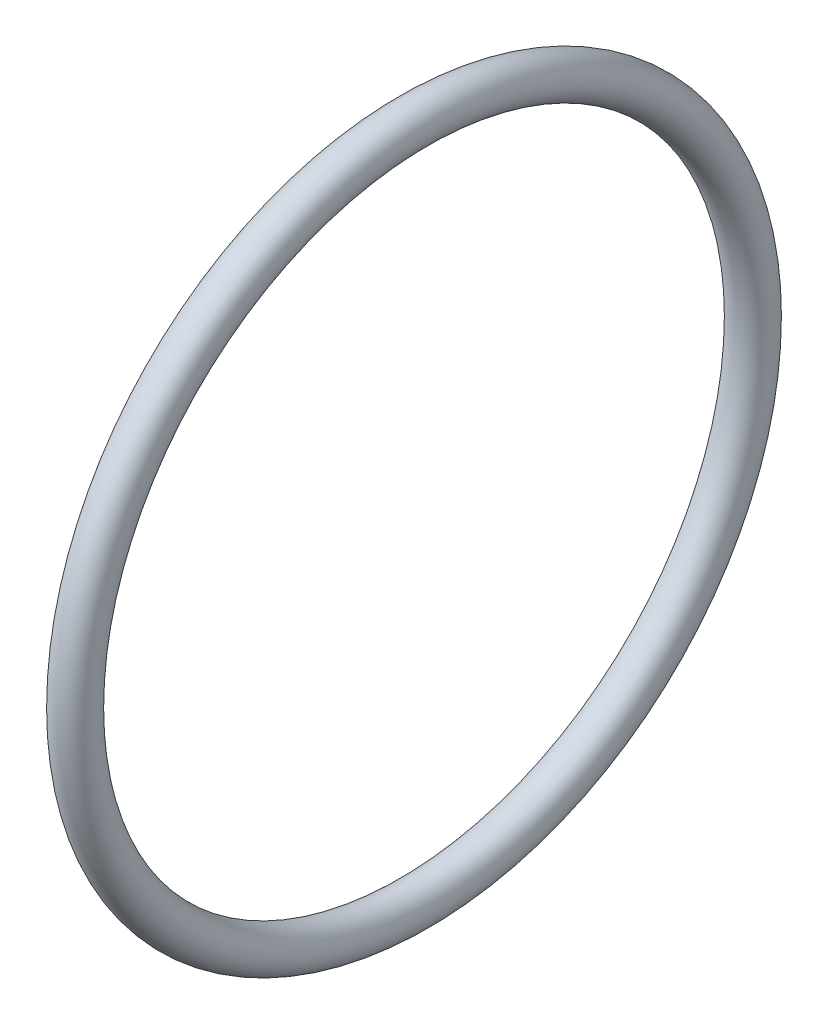
SolidWorks part; units mm, degrees
ref_plane "Front Plane" through (0, 0, 0) normal (0, 0, 1) x (1, 0, 0)
ref_plane "Top Plane" through (0, 0, 0) normal (0, 1, 0) x (1, 0, 0)
ref_plane "Right Plane" through (0, 0, 0) normal (1, 0, 0) x (0, 0, -1)
sketch "Sketch2" plane through (0, 0, 0) normal (0, 0, 1) x (1, 0, 0)
  line L0 (0, 0) -> (58.591, 0) construction
  line L2 (0, 0) -> (18.4, 0)
  line L3 (0, 0) -> (0, 2.5)
  line L4 (0, 2.5) -> (18.4, 2.5)
  line L5 (18.4, 0) -> (18.4, 2.5)
  line L6 (6.0094, 2.5) -> (6.0094, 6)
  line L11 (6.0094, 6) -> (9.9794, 6)
  line L16 (12.9794, 6) -> (12.9794, 3)
  line L17 (12.9794, 3) -> (13.6398, 3)
  line L18 (13.6398, 3) -> (13.6398, 2.5)
  line L19 (13.6398, 2.5) -> (6.0094, 2.5)
  line L22 (13.6398, 2.5) -> (16.1198, 2.5)
  line L23 (13.6398, 2.5) -> (13.6398, 4)
  line L24 (13.6398, 4) -> (16.1198, 4)
  line L25 (16.1198, 2.5) -> (16.1198, 4)
  line L27 (6.0094, 6) -> (9.9794, 6)
  line L28 (6.0094, 6) -> (6.0094, 9)
  line L29 (6.0094, 9) -> (9.9794, 9)
  line L30 (9.9794, 6) -> (9.9794, 9)
  line L31 (6.0094, 9) -> (6.0094, 8.25)
  line L32 (6.0094, 8.25) -> (5.0094, 8.25)
  line L33 (8.6609, 22.001) -> (8.6609, 12.476) construction
  line L34 (5.0094, 12.476) -> (12.3124, 12.476)
  line L35 (9.9794, 9) -> (12.3124, 9)
  line L36 (5.0094, 7.9375) -> (1.8344, 7.9375)
  line L37 (5.0094, 8.25) -> (5.0094, 12.476)
  line L38 (5.0094, 7.9375) -> (5.0094, 13.9365)
  line L39 (5.0094, 13.9365) -> (1.8344, 13.9365)
  line L40 (1.8344, 7.9375) -> (1.8344, 13.9365)
  line L41 (5.0094, 22.001) -> (12.3124, 22.001)
  line L42 (5.0094, 22.001) -> (5.0094, 30.1625)
  line L43 (5.0094, 30.1625) -> (12.3124, 30.1625)
  line L44 (12.3124, 22.001) -> (12.3124, 30.1625)
  line L49 (16.6398, 22.001) -> (16.6398, 7.5)
  line L51 (23.0198, 7.5) -> (23.0198, 6.5)
  line L54 (16.1198, 4) -> (13.6398, 4)
  line L56 (18.0398, 7.5) -> (23.0198, 7.5)
  line L57 (13.3124, 22.001) -> (16.6398, 22.001)
  line L58 (16.1198, 3.5) -> (20.0198, 3.5)
  line L59 (29.9098, 14) -> (26.9098, 11)
  line L60 (4.0094, 31.75) -> (18.0398, 31.75)
  line L61 (18.0398, 7.5) -> (23.0198, 7.5)
  line L62 (18.0398, 7.5) -> (18.0398, 12)
  line L63 (18.0398, 12) -> (23.0198, 12)
  line L64 (23.0198, 7.5) -> (23.0198, 12)
  line L65 (18.0398, 31.75) -> (18.0398, 12)
  line L66 (23.0198, 11) -> (26.9098, 11)
  line L67 (34.8098, 23) -> (31.3098, 19.5)
  line L68 (35.8098, 31) -> (38.7998, 33.99)
  line L69 (29.9098, 14) -> (29.9098, 15)
  line L70 (29.9098, 15) -> (22.9398, 15)
  line L71 (22.9398, 15) -> (21.0398, 15)
  line L72 (18.0398, 7.5) -> (16.6398, 7.5)
  line L73 (21.0398, 15) -> (21.0398, 43)
  line L74 (19.5798, 40) -> (9.6198, 40)
  line L75 (9.6198, 40) -> (4.0094, 40)
  line L76 (21.0398, 43) -> (19.5798, 43)
  line L77 (22.9398, 15) -> (29.9098, 15)
  line L78 (22.9398, 15) -> (22.9398, 21)
  line L79 (22.9398, 21) -> (29.9098, 21)
  line L80 (29.9098, 15) -> (29.9098, 21)
  line L81 (9.6198, 40) -> (19.5798, 40)
  line L82 (9.6198, 40) -> (9.6198, 50)
  line L83 (9.6198, 50) -> (19.5798, 50)
  line L84 (19.5798, 40) -> (19.5798, 50)
  line L85 (4.0094, 40) -> (4.0094, 31.75)
  line L86 (12.9794, 3) -> (12.9794, 2.5)
  line L87 (31.3098, 19.5) -> (29.9098, 19.5)
  line L88 (21.4694, 63.5) -> (21.4694, 51.308)
  line L89 (21.4694, 63.5) -> (25.9398, 63.5)
  line L90 (25.9398, 63.5) -> (25.9398, 25)
  line L91 (27.8398, 25) -> (25.9398, 25)
  line L92 (9.6198, 48) -> (8.1598, 48)
  line L93 (8.1598, 48) -> (8.1598, 53.476)
  line L94 (8.1598, 53.476) -> (19.5798, 53.476)
  line L95 (19.5798, 53.476) -> (19.5798, 50)
  line L96 (13.8698, 63.001) -> (13.8698, 53.476) construction
  line L97 (8.1598, 63.001) -> (19.5798, 63.001)
  line L98 (8.1598, 63.001) -> (8.1598, 68.2625)
  line L99 (8.1598, 68.2625) -> (19.5798, 68.2625)
  line L100 (19.5798, 63.001) -> (19.5798, 68.2625)
  line L101 (12.9794, 6) -> (11.9794, 6)
  line L102 (8.1598, 44.825) -> (4.9848, 44.825)
  line L103 (8.1598, 44.825) -> (8.1598, 54.9365)
  line L104 (8.1598, 54.9365) -> (4.9848, 54.9365)
  line L106 (9.9794, 6) -> (10.8794, 6)
  line L107 (27.8398, 25) -> (34.8098, 25)
  line L108 (34.8098, 25) -> (34.8098, 23)
  line L109 (0, 0) -> (-2, 0)
  line L110 (0, 0) -> (0, 11)
  line L111 (27.8398, 25) -> (34.8098, 25)
  line L112 (27.8398, 25) -> (27.8398, 32.5)
  line L113 (27.8398, 32.5) -> (34.8098, 32.5)
  line L114 (34.8098, 25) -> (34.8098, 32.5)
  line L115 (35.8098, 31) -> (34.8098, 31)
  line L116 (27.8398, 32.5) -> (27.8398, 64.5)
  line L117 (20.5373, 74.025) -> (6.2023, 74.025)
  line L118 (6.2023, 74.025) -> (6.2023, 76.2)
  line L119 (38.7998, 47.29) -> (30.8398, 55.25)
  line L120 (0, 11) -> (-2, 11)
  line L121 (38.7998, 43.815) -> (30.8623, 43.815)
  line L123 (-4.8152, 69.85) -> (1.5348, 76.2)
  line L124 (38.7998, 47.29) -> (38.7998, 33.99)
  line L125 (-2, 0) -> (-2, 11)
  line L126 (38.7998, 37.465) -> (30.8623, 37.465)
  line L127 (30.8623, 43.815) -> (30.8623, 37.465)
  line L128 (6.0094, 2.5) -> (6.0094, 0)
  line L129 (-0.0152, 63.5) -> (-0.0152, 30)
  line L132 (4.9848, 63.5) -> (-0.0152, 63.5)
  line L136 (-1.8152, 30) -> (-11.7752, 30)
  line L138 (-13.7752, 25.4) -> (-2, 25.4)
  line L139 (-2, 25.4) -> (-2, 11.5)
  line L140 (27.8398, 64.5) -> (20.5373, 64.5)
  line L141 (-1.8152, 30) -> (-11.7752, 30)
  line L142 (-1.8152, 30) -> (-1.8152, 39)
  line L143 (-1.8152, 39) -> (-11.7752, 39)
  line L144 (-11.7752, 30) -> (-11.7752, 39)
  line L145 (20.5373, 64.5) -> (20.5373, 74.025)
  line L146 (-12.7752, 37) -> (-12.7752, 47.29)
  line L147 (-12.7752, 37) -> (-11.7752, 37)
  line L148 (30.8398, 55.25) -> (30.8398, 76.2)
  line L149 (11.9794, 6) -> (11.9794, 5.45)
  line L154 (-2, 11.5) -> (0.5, 11.5)
  line L155 (4.9848, 60.6197) -> (24.0348, 60.6197)
  line L160 (4.9848, 60.6197) -> (4.9848, 55.8572)
  line L161 (4.9848, 55.8572) -> (24.0348, 55.8572)
  line L166 (24.0348, 60.6197) -> (24.0348, 55.8572)
  line L167 (4.9848, 60.6197) -> (24.0348, 55.8572) construction
  line L172 (4.9848, 55.8572) -> (24.0348, 60.6197) construction
  line L173 (24.0348, 62.2072) -> (25.9398, 62.2072)
  line L174 (11.9794, 5.45) -> (10.8794, 5.45)
  line L175 (10.8794, 6) -> (10.8794, 5.45)
  line L176 (24.0348, 62.2072) -> (24.0348, 54.2697)
  line L177 (24.0348, 54.2697) -> (25.9398, 54.2697)
  line L178 (25.9398, 62.2072) -> (25.9398, 54.2697)
  line L179 (24.0348, 62.2072) -> (25.9398, 54.2697) construction
  line L180 (24.0348, 54.2697) -> (25.9398, 62.2072) construction
  line L181 (3, 19.6197) -> (15.7, 19.6197)
  line L182 (3, 19.6197) -> (3, 14.8572)
  line L183 (3, 14.8572) -> (15.7, 14.8572)
  line L184 (15.7, 19.6197) -> (15.7, 14.8572)
  line L185 (3, 19.6197) -> (15.7, 14.8572) construction
  line L186 (3, 14.8572) -> (15.7, 19.6197) construction
  line L187 (15.7, 21.2072) -> (16.6398, 21.2072)
  line L188 (15.7, 21.2072) -> (15.7, 13.2697)
  line L189 (15.7, 13.2697) -> (16.6398, 13.2697)
  line L190 (16.6398, 21.2072) -> (16.6398, 13.2697)
  line L191 (15.7, 21.2072) -> (16.6398, 13.2697) construction
  line L192 (15.7, 13.2697) -> (16.6398, 21.2072) construction
  line L193 (0.5, 11.5) -> (0.5, 6.9375)
  line L194 (0.5, 6.9375) -> (1.8344, 6.9375)
  line L195 (23.0198, 6.5) -> (20.0198, 3.5)
  line L196 (4.9848, 63.5) -> (4.9848, 54.9365)
  line L197 (3, 43.825) -> (4.9848, 43.825)
  line L198 (1.8344, 6.9375) -> (1.8344, 7.9375)
  line L199 (6.0094, 0) -> (12.9794, 0)
  line L200 (12.9794, 0) -> (12.9794, 2.5)
  line L201 (18.0398, 31.75) -> (18.0398, 35.875)
  line L202 (18.0398, 35.875) -> (21.0398, 35.875)
  line L203 (30.8398, 76.2) -> (6.2023, 76.2)
  line L204 (2.7573, 69.85) -> (7.2023, 69.85) construction
  line L205 (7.2023, 67.4688) -> (26.2523, 67.4688)
  line L206 (7.2023, 74.025) -> (7.2023, 64.5)
  line L207 (7.2023, 64.5) -> (-1.8152, 64.5)
  line L208 (-1.8152, 64.5) -> (-1.8152, 39)
  line L209 (-12.7752, 47.29) -> (-4.8152, 55.25)
  line L210 (-4.8152, 55.25) -> (-4.8152, 69.85)
  line L211 (7.2023, 67.4688) -> (7.2023, 72.2312)
  line L212 (7.2023, 72.2312) -> (26.2523, 72.2313)
  line L213 (26.2523, 67.4688) -> (26.2523, 72.2313)
  line L214 (26.2523, 73.8187) -> (30.8398, 73.8187)
  line L215 (26.2523, 73.8187) -> (26.2523, 65.8813)
  line L216 (26.2523, 65.8813) -> (30.8398, 65.8813)
  line L217 (30.8398, 73.8187) -> (30.8398, 65.8813)
  line L218 (2.7573, 72.2313) -> (24.9823, 72.2313)
  line L219 (2.7573, 72.2313) -> (2.7573, 67.4687)
  line L220 (2.7573, 67.4687) -> (24.9823, 67.4687)
  line L221 (24.9823, 72.2313) -> (24.9823, 67.4687)
  line L222 (24.9823, 69.85) -> (20.5373, 69.85) construction
  line L223 (21.4694, 51.308) -> (22.9398, 51.308)
  line L224 (22.9398, 51.308) -> (22.9398, 21)
  line L225 (13.6398, 4) -> (13.6398, 12.2697)
  line L226 (13.6398, 12.2697) -> (13.3124, 12.2697)
  line L227 (13.3124, 12.2697) -> (13.3124, 22.001)
  line L228 (12.3124, 9) -> (12.3124, 12.476)
  line L229 (-1.8152, 30) -> (-0.0152, 30)
  line L230 (8.1598, 65.6317) -> (2.7573, 65.6317) construction
  line L231 (19.5798, 65.6317) -> (24.9823, 65.6317) construction
  line L232 (1.5348, 76.2) -> (6.2023, 76.2)
  line L233 (-11.7752, 30) -> (-13.7752, 30)
  line L234 (-13.7752, 30) -> (-13.7752, 25.4)
  line L235 (3, 13.9365) -> (3, 43.825)
  line L236 (4.9848, 54.9365) -> (4.9848, 44.825)
  line L237 (4.9848, 43.825) -> (4.9848, 44.825)
  circle A0 centre (26.8898, 25.95) radius 0.95
  circle A1 centre (21.9898, 15.95) radius 0.95
  circle A2 centre (17.3398, 8.2) radius 0.7
  circle A3 centre (10.4294, 6.45) radius 0.45
  circle A4 centre (-0.9152, 30.9) radius 0.9
  point P7 (24.9873, 58.2385)
  point P131 (16.1699, 17.2385)
  point P135 (14.5098, 58.2385)
  point P146 (9.35, 17.2385)
sketch "Sketch3" plane through (0, 0, 0) normal (0, 0, 1) x (1, 0, 0)
  circle A0 centre (21.9898, 15.95) radius 0.95 construction
  circle A1 centre (21.9898, 15.95) radius 0.95
revolve "Revolve1" add sketch "Sketch3" angle 360 about L0
